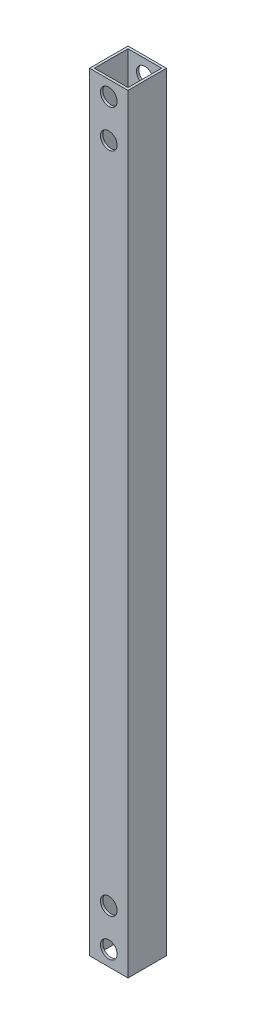
SolidWorks part; units mm, degrees
material "1060 Alloy"
ref_plane "Front Plane" through (0, 0, 0) normal (0, 0, 1) x (1, 0, 0)
ref_plane "Top Plane" through (0, 0, 0) normal (0, 1, 0) x (1, 0, 0)
ref_plane "Right Plane" through (0, 0, 0) normal (1, 0, 0) x (0, 0, -1)
sketch "Sketch1" plane through (0, 0, 0) normal (0, 1, 0) x (1, 0, 0)
  line L1 (-12.7, -12.7) -> (12.7, -12.7)
  line L2 (-12.7, -12.7) -> (-12.7, 12.7)
  line L3 (-12.7, 12.7) -> (12.7, 12.7)
  line L4 (12.7, -12.7) -> (12.7, 12.7)
  line L5 (-12.7, -12.7) -> (12.7, 12.7) construction
  line L6 (-12.7, 12.7) -> (12.7, -12.7) construction
  point P0 (0, 0)
  dimension "D1" = 25.4
extrude "Extrude-Thin1" add sketch "Sketch1" along normal blind 508 thin thin type one direction reverse wall 1.5875
sketch "Sketch2" plane through (0, 0, -12.7) normal (0, 0, -1) x (-1, 0, 0)
  line L0 (0, 508) -> (0, 0) construction
  line L1 (-12.7, 508) -> (12.7, 508) construction
  line L2 (-12.7, 0) -> (12.7, 0) construction
  line L3 (12.7, 254) -> (-12.7, 254) construction
  line L4 (12.7, 508) -> (12.7, 0) construction
  line L5 (-12.7, 508) -> (-12.7, 0) construction
  point P6 (0, 498)
  point P7 (0, 473)
  point P14 (0, 35)
  point P15 (0, 10)
  dimension "D1" = 10
  dimension "D2" = 25
hole_wizard "M10 Clearance Hole1" positions "Sketch3" profile "Sketch4" hole size "M10" standard "ANSI Metric" end condition through all
sketch "Sketch3" plane through (0, 0, -12.7) normal (0, 0, -1) x (-1, 0, 0)
  point P0 (0, 498)
  point P3 (0, 473)
  point P6 (0, 35)
  point P9 (0, 10)
sketch "Sketch4" plane through (0, 498, -12.7) normal (1, 0, 0) x (0, 1, 0)
  line L0 (0, 0) -> (0, 25.4)
  line L1 (0, 25.4) -> (5.5, 25.4)
  line L2 (5.5, 25.4) -> (5.5, 0.025)
  line L3 (5.5, 0.025) -> (5.525, 0)
  line L5 (5.525, 0) -> (0, 0)
  line L6 (-5.5, 0.025) -> (-5.525, 0) construction
  line L11 (0, -6.35) -> (0, 107.95) construction
  dimension "Thru Hole Dia." = 11
  dimension "Thru Hole Depth" = 25.4
  dimension "Near C'Sink Dia." = 11.05
  dimension "Near C'Sink Angle" = 90
